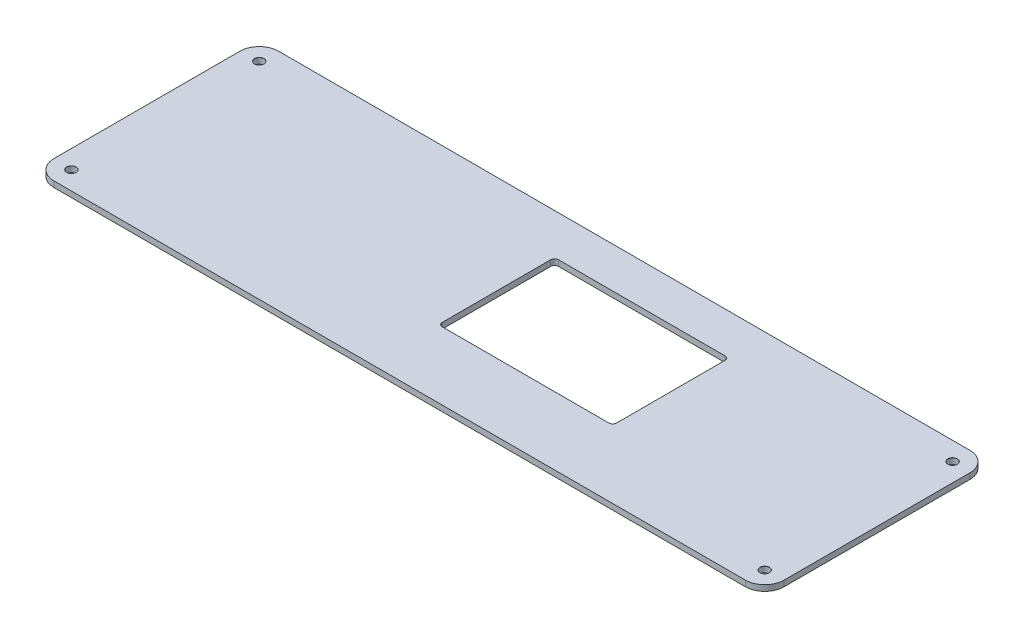
SolidWorks part; units mm, degrees
ref_plane "Front Plane" through (0, 0, 0) normal (0, 0, 1) x (1, 0, 0)
ref_plane "Top Plane" through (0, 0, 0) normal (0, 1, 0) x (1, 0, 0)
ref_plane "Right Plane" through (0, 0, 0) normal (1, 0, 0) x (0, 0, -1)
sketch "Sketch1" plane through (0, 0, 0) normal (0, 1, 0) x (1, 0, 0)
  line L1 (94.25, -29) -> (-94.25, -29)
  line L2 (94.25, -29) -> (94.25, 29)
  line L3 (94.25, 29) -> (-94.25, 29)
  line L4 (-94.25, -29) -> (-94.25, 29)
  line L5 (94.25, -29) -> (-94.25, 29) construction
  line L6 (94.25, 29) -> (-94.25, -29) construction
  point P0 (0, 0)
  dimension "D1" = 58
  dimension "D2" = 188.5
extrude "Boss-Extrude1" add sketch "Sketch1" along normal blind 1.5
fillet "Fillet1" radius 5 4 edges at (-94.25, 0.75, -29) (94.25, 0.75, -29) (94.25, 0.75, 29) (-94.25, 0.75, 29)
hole_wizard "M2 Clearance Hole1" positions "Sketch2" profile "Sketch3" hole size "M2" standard "ANSI Metric" end condition up to next
sketch "Sketch2" plane through (0, 1.5, 0) normal (0, 1, 0) x (1, 0, 0)
  line L0 (-89.5, -24.25) -> (-89.5, 24.25) construction
  line L1 (-89.5, 24.25) -> (89.5, 24.25) construction
  line L2 (89.5, 24.25) -> (-89.5, -24.25) construction
  line L6 (89.5, 24.25) -> (89.5, -24.25) construction
  line L7 (89.5, -24.25) -> (-89.5, -24.25) construction
  point P0 (-89.5, 24.25)
  point P2 (89.5, 24.25)
  point P4 (89.5, -24.25)
  point P6 (-89.5, -24.25)
  point P16 (0, 0)
  dimension "D1" = 179
  dimension "D2" = 48.5
sketch "Sketch3" plane through (-89.5, 1.5, -24.25) normal (1, 0, 0) x (0, 0, 1)
  line L0 (0, 0) -> (0, 1.5)
  line L1 (0, 1.5) -> (1.2, 1.5)
  line L2 (1.2, 1.5) -> (1.2, 0.025)
  line L3 (1.2, 0.025) -> (1.225, 0)
  line L5 (1.225, 0) -> (0, 0)
  line L6 (-1.2, 0.025) -> (-1.225, 0) construction
  line L11 (0, -6.35) -> (0, 107.95) construction
  dimension "Thru Hole Dia." = 2.4
  dimension "Thru Hole Depth" = 1.5
  dimension "Near C'Sink Dia." = 2.45
  dimension "Near C'Sink Angle" = 90
sketch "Sketch4" plane through (0, 1.5, 0) normal (0, 1, 0) x (1, 0, 0)
  line L17 (37.5, -11.5) -> (-7.5, -11.5)
  line L18 (37.5, -11.5) -> (37.5, 18.5)
  line L19 (37.5, 18.5) -> (-7.5, 18.5)
  line L20 (-7.5, -11.5) -> (-7.5, 18.5)
  line L21 (37.5, -11.5) -> (-7.5, 18.5) construction
  line L22 (37.5, 18.5) -> (-7.5, -11.5) construction
  point P0 (15, 3.5)
  point P5 (0, 0)
  point P6 (19.5852, 4.0521)
  dimension "D1" = 15
  dimension "D2" = 45
  dimension "D3" = 30
  dimension "D4" = 3.5
extrude "Cut-Extrude1" cut sketch "Sketch4" against normal through all
fillet "Fillet2" radius 1 4 edges at (37.5, 0.75, 11.5) (-7.5, 0.75, 11.5) (-7.5, 0.75, -18.5) (37.5, 0.75, -18.5)
